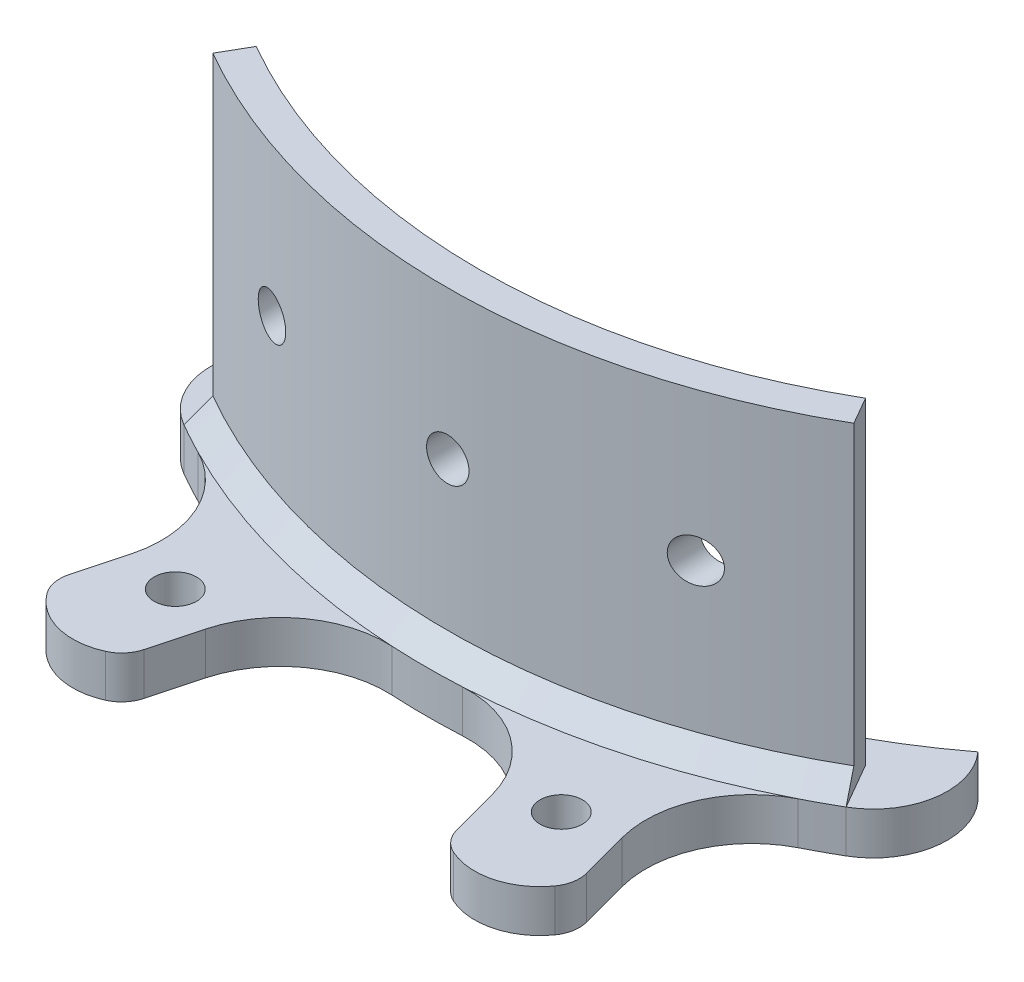
SolidWorks part; units mm, degrees
ref_plane "Front Plane" through (0, 0, 0) normal (0, 0, 1) x (1, 0, 0)
ref_plane "Top Plane" through (0, 0, 0) normal (0, 1, 0) x (1, 0, 0)
ref_plane "Right Plane" through (0, 0, 0) normal (1, 0, 0) x (0, 0, -1)
sketch "Sketch1" plane through (0, 0, 0) normal (0, 1, 0) x (1, 0, 0)
  line L0 (0, 0) -> (0, -54.5) construction
  line L1 (0, 0) -> (0, 55) construction
  line L2 (0, 0) -> (-27.25, -47.1984) construction
  line L3 (0, 0) -> (27.25, -47.1984) construction
  line L4 (-27.25, -47.1984) -> (-25.25, -43.7343)
  line L5 (25.25, -43.7343) -> (27.25, -47.1984)
  arc A0 (-27.25, -47.1984) -> (27.25, -47.1984) centre (0, 0) ccw
  arc A1 (-25.25, -43.7343) -> (25.25, -43.7343) centre (0, 0) ccw
  dimension "D1" = 54.5
  dimension "D2" = 55
  dimension "D3" = 150
  dimension "D4" = 54.5
  dimension "D5" = 4
extrude "Boss-Extrude1" add sketch "Sketch1" along normal blind 10 contours A1 L4 A0 L5
sketch "Sketch3" plane through (0, 0, 0) normal (0, -1, 0) x (1, 0, 0)
  line L0 (0, 0) -> (-27.25, 47.1984) construction
  line L1 (-27.25, 47.1984) -> (27.25, 47.1984) construction
  line L2 (27.25, 47.1984) -> (0, 0) construction
  line L3 (-30.25, 52.3945) -> (-28.75, 49.7965)
  line L4 (28.75, 49.7965) -> (30.25, 52.3945)
  arc A0 (-27.25, 47.1984) -> (27.25, 47.1984) centre (0, 0) cw construction
  arc A1 (-28.75, 49.7965) -> (28.75, 49.7965) centre (0, 0) cw
  arc A2 (-30.25, 52.3945) -> (30.25, 52.3945) centre (0, 0) cw
  dimension "D1" = 3
  dimension "D2" = 3
extrude "Boss-Extrude2" add sketch "Sketch3" against normal blind 30 separate body
sketch "Sketch4" plane through (0, 0, 0) normal (0, -1, 0) x (1, 0, 0)
  line L0 (0, 0) -> (-27.25, 47.1984) construction
  line L1 (-27.25, 47.1984) -> (27.25, 47.1984) construction
  line L2 (27.25, 47.1984) -> (0, 0) construction
  arc A0 (-27.25, 47.1984) -> (27.25, 47.1984) centre (0, 0) cw construction
  arc A1 (-24.25, 42.0022) -> (24.25, 42.0022) centre (0, 0) cw
  arc A2 (-31.25, 54.1266) -> (31.25, 54.1266) centre (0, 0) cw
  arc A3 (-31.25, 54.1266) -> (-24.25, 42.0022) centre (-27.75, 48.0644) ccw
  arc A4 (31.25, 54.1266) -> (24.25, 42.0022) centre (27.75, 48.0644) cw
  dimension "D1" = 6
  dimension "D2" = 8
extrude "Boss-Extrude3" add sketch "Sketch4" along normal blind 4
chamfer "Chamfer1" distance 2 angle 45 2 edges at (0, 0, 60.5) (0, 0, 50.5)
sketch "Sketch5" plane through (0, 0, 0) normal (0, 0, 1) x (1, 0, 0)
  line L0 (-30.25, 16) -> (30.25, 16) construction
  line L1 (-30.25, 30) -> (-30.25, 2) construction
  line L2 (30.25, 30) -> (30.25, 2) construction
  line L3 (0, 16) -> (0, 5.2868) construction
  circle A0 centre (0, 16) radius 2
  circle A1 centre (-20, 16) radius 2
  circle A2 centre (20, 16) radius 2
  dimension "D1" = 4
  dimension "D2" = 4
  dimension "D3" = 20
extrude "Cut-Extrude1" cut sketch "Sketch5" against normal through all both and the other way through all
sketch "Sketch6" plane through (0, -4, 0) normal (0, -1, 0) x (1, 0, 0)
  line L0 (0, 0) -> (31.25, 54.1266) construction
  line L1 (31.25, 54.1266) -> (0, 62.5) construction
  line L2 (0, 62.5) -> (-31.25, 54.1266) construction
  line L3 (-31.25, 54.1266) -> (0, 0) construction
  line L4 (15.625, 58.3133) -> (18.9896, 70.8703) construction
  line L5 (20.954, 58.8828) -> (24.4147, 71.7982)
  line L6 (11.2947, 61.471) -> (14.7554, 74.3864)
  line L7 (20.4546, 57.0192) -> (23.8193, 69.5762) construction
  line L8 (10.7954, 59.6074) -> (14.16, 72.1644) construction
  line L9 (0, 54.5) -> (0, 42.0385) construction
  line L10 (0, 0) -> (0, 54.5) construction
  line L13 (-20.954, 58.8828) -> (-24.4147, 71.7982)
  line L14 (-11.2947, 61.471) -> (-14.7554, 74.3864)
  arc A0 (31.25, 54.1266) -> (-31.25, 54.1266) centre (0, 0) ccw construction
  circle A2 centre (18.2132, 67.9726) radius 2
  arc A3 (20.954, 58.8828) -> (11.2947, 61.471) centre (0, 0) ccw
  arc A4 (1.6355, 64.0592) -> (11.2947, 61.471) centre (-9.6593, 2.5882) cw
  arc A5 (-20.954, 58.8828) -> (-11.2947, 61.471) centre (0, 0) cw
  arc A8 (16.4154, 76.3427) -> (23.9552, 74.3224) centre (18.9541, 70.7378) cw
  arc A9 (24.4147, 71.7982) -> (23.9552, 74.3224) centre (21.5169, 72.5747) ccw
  arc A10 (14.7554, 74.3864) -> (16.4154, 76.3427) centre (17.6532, 73.6099) cw
  circle A11 centre (-18.2132, 67.9726) radius 2
  arc A12 (-20.954, 58.8828) -> (-11.2947, 61.471) centre (0, 0) cw
  arc A13 (-24.4147, 71.7982) -> (-23.9552, 74.3224) centre (-21.5169, 72.5747) cw
  arc A14 (-14.7554, 74.3864) -> (-16.4154, 76.3427) centre (-17.6532, 73.6099) ccw
  arc A15 (-16.4154, 76.3427) -> (-23.9552, 74.3224) centre (-18.9541, 70.7378) ccw
  dimension "D4" = 4
  dimension "D6" = 3
  dimension "D1" = 13
  dimension "D2" = 5
  dimension "D5" = 3
  dimension "D3" = 5
extrude "Boss-Extrude4" add sketch "Sketch6" against normal blind 4
fillet "Fillet1" radius 10 4 edges at (20.954, -2, 58.8828) (11.2947, -2, 61.471) (-20.954, -2, 58.8828) (-11.2947, -2, 61.471)
sketch "Sketch7" plane through (0, 0, 0) normal (0, 1, 0) x (1, 0, 0)
  circle A1 centre (0, 0) radius 54.5
extrude "Cut-Extrude2" cut sketch "Sketch7" against normal through all both and the other way through all
